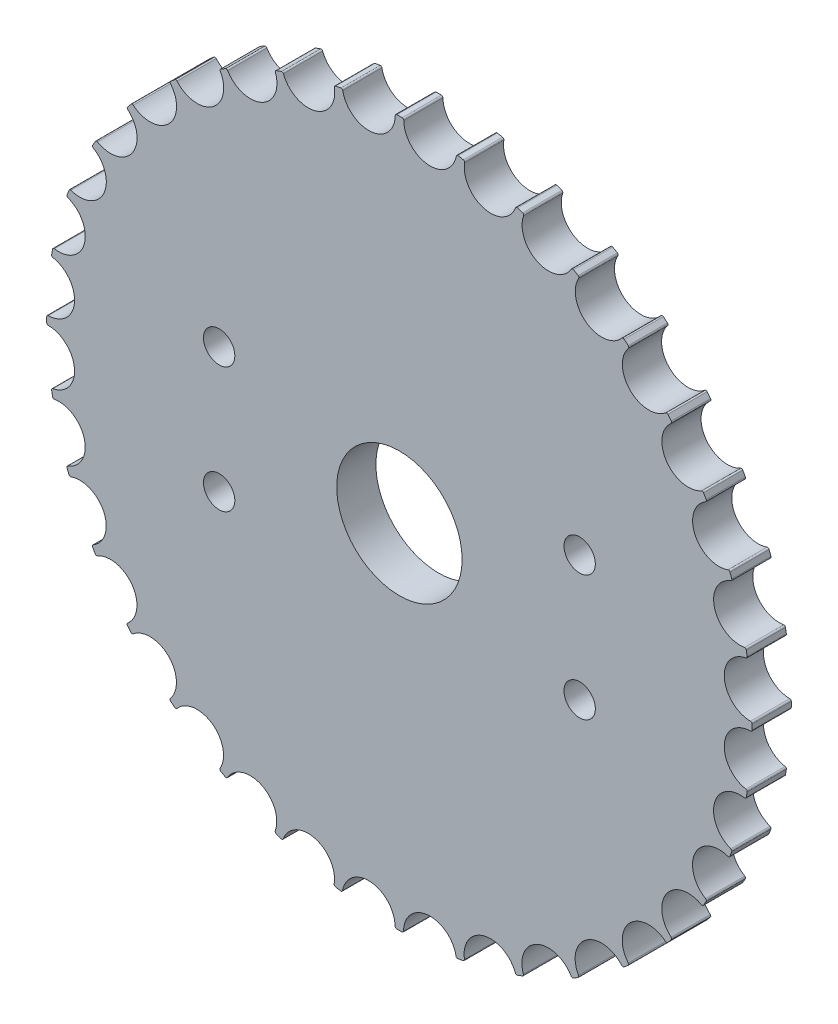
SolidWorks part; units mm, degrees
ref_plane "정면" through (0, 0, 0) normal (0, 0, 1) x (1, 0, 0)
ref_plane "윗면" through (0, 0, 0) normal (0, 1, 0) x (1, 0, 0)
ref_plane "우측면" through (0, 0, 0) normal (1, 0, 0) x (0, 0, -1)
sketch "스케치1" plane through (0, 0, 0) normal (0, 0, 1) x (1, 0, 0)
  circle A0 centre (0, 0) radius 45
extrude "보스-돌출1" add sketch "스케치1" along normal blind 5
sketch "스케치2" plane through (0, 0, 5) normal (0, 0, 1) x (1, 0, 0)
  line L0 (0, 0) -> (0, 53.4651) construction
  line L1 (0, 0) -> (9.1386, 52.0133) construction
  line L2 (0, 0) -> (-9.7027, 52.5525) construction
  circle A0 centre (3.9357, 44.8276) radius 3.38
  circle A2 centre (0, 0) radius 45 construction
  circle A6 centre (11.6601, 43.4631) radius 3.38
  circle A7 centre (19.0303, 40.778) radius 3.38
  circle A8 centre (25.8222, 36.854) radius 3.38
  circle A9 centre (31.8295, 31.8101) radius 3.38
  circle A10 centre (36.8697, 25.7997) radius 3.38
  circle A11 centre (40.7897, 19.0054) radius 3.38
  circle A12 centre (43.4702, 11.6336) radius 3.38
  circle A13 centre (44.83, 3.9083) radius 3.38
  circle A14 centre (44.8276, -3.9357) radius 3.38
  circle A15 centre (43.4631, -11.6601) radius 3.38
  circle A16 centre (40.778, -19.0303) radius 3.38
  circle A17 centre (36.854, -25.8222) radius 3.38
  circle A18 centre (31.8101, -31.8295) radius 3.38
  circle A19 centre (25.7997, -36.8697) radius 3.38
  circle A20 centre (19.0054, -40.7897) radius 3.38
  circle A21 centre (11.6336, -43.4702) radius 3.38
  circle A22 centre (3.9083, -44.83) radius 3.38
  circle A23 centre (-3.9357, -44.8276) radius 3.38
  circle A24 centre (-11.6601, -43.4631) radius 3.38
  circle A25 centre (-19.0303, -40.778) radius 3.38
  circle A26 centre (-25.8222, -36.854) radius 3.38
  circle A27 centre (-31.8295, -31.8101) radius 3.38
  circle A28 centre (-36.8697, -25.7997) radius 3.38
  circle A29 centre (-40.7897, -19.0054) radius 3.38
  circle A30 centre (-43.4702, -11.6336) radius 3.38
  circle A31 centre (-44.83, -3.9083) radius 3.38
  circle A32 centre (-44.8276, 3.9357) radius 3.38
  circle A33 centre (-43.4631, 11.6601) radius 3.38
  circle A34 centre (-40.778, 19.0303) radius 3.38
  circle A35 centre (-36.854, 25.8222) radius 3.38
  circle A36 centre (-31.8101, 31.8295) radius 3.38
  circle A37 centre (-25.7997, 36.8697) radius 3.38
  circle A38 centre (-19.0054, 40.7897) radius 3.38
  circle A39 centre (-11.6336, 43.4702) radius 3.38
  circle A40 centre (-3.9083, 44.83) radius 3.38
  dimension "D1" = 106.9058
  dimension "D2" = 36
extrude "컷-돌출2" cut sketch "스케치2" against normal blind 50
fillet "필렛1" radius 0.2 72 edges at (44.9965, -0.5599, 2.5) (44.9969, 0.5324, 2.5) (44.4101, 7.2621, 2.5) (44.2208, 8.338, 2.5) (42.4744, 14.8635, 2.5) (42.1011, 15.8901, 2.5) (39.2481, 22.0133, 2.5) (38.7022, 22.9595, 2.5) (34.8293, 28.4943, 2.5) (34.1273, 29.3313, 2.5) (29.3521, 34.1094, 2.5) (28.5156, 34.8118, 2.5) (22.9832, 38.6882, 2.5) (22.0373, 39.2346, 2.5) (44.4057, -7.2893, 2.5) (44.2157, -8.365, 2.5) (42.4653, -14.8895, 2.5) (42.0914, -15.9159, 2.5) (39.2346, -22.0373, 2.5) (38.6882, -22.9832, 2.5) (34.8118, -28.5156, 2.5) (34.1094, -29.3521, 2.5) (29.3313, -34.1273, 2.5) (28.4943, -34.8293, 2.5) (22.9595, -38.7022, 2.5) (22.0133, -39.2481, 2.5) (15.8901, -42.1011, 2.5) (14.8635, -42.4744, 2.5) (8.338, -44.2208, 2.5) (7.2621, -44.4101, 2.5) (0.5324, -44.9969, 2.5) (-0.5599, -44.9965, 2.5) (-7.2893, -44.4057, 2.5) (-8.365, -44.2157, 2.5) (-14.8895, -42.4653, 2.5) (-15.9159, -42.0914, 2.5) (-22.0373, -39.2346, 2.5) (-22.9832, -38.6882, 2.5) (-28.5156, -34.8118, 2.5) (-29.3521, -34.1094, 2.5) (-34.1273, -29.3313, 2.5) (-34.8293, -28.4943, 2.5) (-38.7022, -22.9595, 2.5) (-39.2481, -22.0133, 2.5) (-42.1011, -15.8901, 2.5) (-42.4744, -14.8635, 2.5) (-44.2208, -8.338, 2.5) (-44.4101, -7.2621, 2.5) (-44.9969, -0.5324, 2.5) (-44.9965, 0.5599, 2.5) (-44.4057, 7.2893, 2.5) (-44.2157, 8.365, 2.5) (-42.4653, 14.8895, 2.5) (-42.0914, 15.9159, 2.5) (-39.2346, 22.0373, 2.5) (-38.6882, 22.9832, 2.5) (-34.8118, 28.5156, 2.5) (-34.1094, 29.3521, 2.5) (-29.3313, 34.1273, 2.5) (-28.4943, 34.8293, 2.5) (-22.0133, 39.2481, 2.5) (-22.9595, 38.7022, 2.5) (-15.8901, 42.1011, 2.5) (-14.8635, 42.4744, 2.5) (-8.338, 44.2208, 2.5) (-7.2621, 44.4101, 2.5) (-0.5324, 44.9969, 2.5) (0.5599, 44.9965, 2.5) (7.2893, 44.4057, 2.5) (8.365, 44.2157, 2.5) (14.8895, 42.4653, 2.5) (15.9159, 42.0914, 2.5)
sketch "스케치4" plane through (0, 0, 5) normal (0, 0, 1) x (1, 0, 0)
  circle A0 centre (0, 0) radius 8
  dimension "D1" = 16
extrude "컷-돌출3" cut sketch "스케치4" against normal blind 10
sketch "스케치5" plane through (0, 0, 5) normal (0, 0, 1) x (1, 0, 0)
  line L0 (-52.1074, 0) -> (52.2141, 0) construction
  line L1 (-52.1074, -15) -> (52.2141, -15)
  line L2 (-52.1074, 15) -> (52.2141, 15)
  line L3 (0, 53.1222) -> (0, -55.2945) construction
  line L4 (-30, 53.1222) -> (-30, -55.2945)
  line L5 (30, 53.1222) -> (30, -55.2945)
  circle A0 centre (-23, 8) radius 2
  circle A1 centre (23, 8) radius 2
  circle A2 centre (23, -8) radius 2
  circle A3 centre (-23, -8) radius 2
  dimension "D5" = 4
  dimension "D7" = 7
  dimension "D6" = 7
  dimension "D1" = 15
  dimension "D2" = 15
  dimension "D3" = 30
  dimension "D4" = 30
extrude "컷-돌출4" cut sketch "스케치5" against normal blind 10 contours A3 | A0 | A1 | A2
